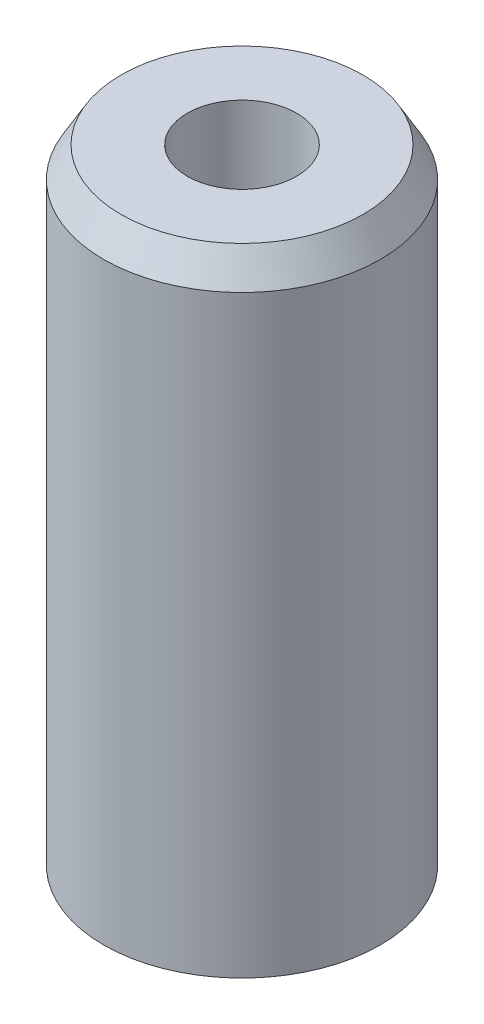
SolidWorks part; units mm, degrees
ref_plane "Front Plane" through (0, 0, 0) normal (0, 0, 1) x (1, 0, 0)
ref_plane "Top Plane" through (0, 0, 0) normal (0, 1, 0) x (1, 0, 0)
ref_plane "Right Plane" through (0, 0, 0) normal (1, 0, 0) x (0, 0, -1)
sketch "Sketch1" plane through (0, 0, 0) normal (0, 1, 0) x (1, 0, 0)
  circle A0 centre (0, 0) radius 5
  dimension "SHAFT_OD" = 10
extrude "Boss-Extrude1" add sketch "Sketch1" along normal blind 23.1796
sketch "Sketch2" plane through (0, 0, 0) normal (0, 1, 0) x (1, 0, 0)
  circle A0 centre (0, 0) radius 1.9771
  dimension "BORE_D" = 3.9542
extrude "Cut-Extrude1" cut sketch "Sketch2" along normal through all
chamfer "Chamfer1" distance 1.0906 angle 30 2 edges at (0, 23.1796, 5) (0, 0, 5) first distance on face at (0, 23.1796, 5) first distance on face at (0, 0, 1.9771)
